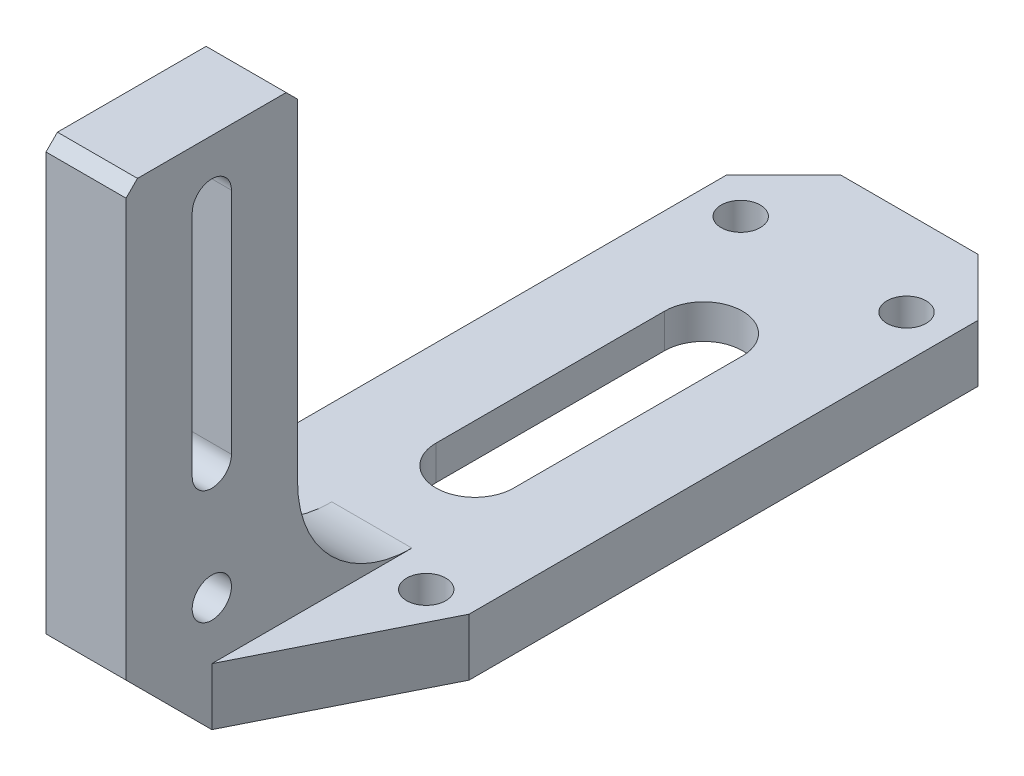
SolidWorks part; units mm, degrees
ref_plane "Front Plane" through (0, 0, 0) normal (0, 0, 1) x (1, 0, 0)
ref_plane "Top Plane" through (0, 0, 0) normal (0, 1, 0) x (1, 0, 0)
ref_plane "Right Plane" through (0, 0, 0) normal (1, 0, 0) x (0, 0, -1)
sketch "Sketch1" plane through (0, 0, 0) normal (0, 1, 0) x (1, 0, 0)
  line L1 (-11, -36) -> (11, -36)
  line L2 (-11, -36) -> (-11, 36)
  line L3 (-11, 36) -> (11, 36)
  line L4 (11, -36) -> (11, 36)
  line L5 (-11, -36) -> (11, 36) construction
  line L6 (-11, 36) -> (11, -36) construction
  point P0 (0, 0)
  dimension "D1" = 22
  dimension "D2" = 72
extrude "Boss-Extrude1" add sketch "Sketch1" along normal blind 5
sketch "Sketch2" plane through (0, 5, 0) normal (0, 1, 0) x (1, 0, 0)
  line L0 (-11, -36) -> (11, -36) construction
  line L1 (-3.5, -36) -> (3.5, -36)
  line L2 (-3.5, -36) -> (-3.5, -21)
  line L3 (-3.5, -21) -> (3.5, -21)
  line L4 (3.5, -36) -> (3.5, -21)
  line L5 (-11, 36) -> (-11, -36) construction
  dimension "D1" = 7
  dimension "D2" = 7.5
  dimension "D3" = 15
extrude "Boss-Extrude2" add sketch "Sketch2" along normal blind 40
chamfer "Chamfer1" distance 1 angle 45 2 edges at (0, 45, 36) (0, 45, 21)
fillet "Fillet1" radius 10 1 edges at (0, 5, 21)
sketch "Sketch5" plane through (0, 0, 0) normal (0, -1, 0) x (1, 0, 0)
  line L0 (11, -36) -> (-11, -36) construction
  line L2 (0, 2) -> (0, -18) construction
  line L3 (3.4, 2) -> (3.4, -18)
  line L4 (-3.4, 2) -> (-3.4, -18)
  line L5 (11, -36) -> (-11, -36) construction
  arc A1 (3.4, 2) -> (-3.4, 2) centre (0, 2) ccw
  arc A2 (-3.4, -18) -> (3.4, -18) centre (0, -18) ccw
  point P2 (0, -36)
  point P4 (0, -18)
  point P9 (0, -8)
  dimension "D2" = 3.4
  dimension "D1" = 18
  dimension "D3" = 20
extrude "Cut-Extrude2" cut sketch "Sketch5" against normal through all
sketch "Sketch6" plane through (0, 5, 0) normal (0, 1, 0) x (1, 0, 0)
  line L0 (11, -36) -> (11, 36) construction
  line L1 (3.5, -36) -> (11, -36)
  line L2 (3.5, -36) -> (3.5, -28.5)
  line L3 (3.5, -28.5) -> (11, -28.5)
  line L4 (11, -36) -> (11, -28.5)
  dimension "D1" = 7.5
extrude "Cut-Extrude3" cut sketch "Sketch6" against normal through all
mirror "Mirror1" about plane through (0, 0, 0) normal (1, 0, 0) of "Cut-Extrude3"
chamfer "Chamfer2" distance 15 distance2 7.5 1 edges at (11, 2.5, 28.5) first distance on face at (11, 2.5, -3.75)
chamfer "Chamfer7" distance 7.5 angle 45 1 edges at (0, 0, 36)
chamfer "Chamfer3" distance 5 angle 45 2 edges at (11, 2.5, -36) (-11, 2.5, -36)
sketch "Sketch8" plane through (0, 0, 0) normal (0, -1, 0) x (1, 0, 0)
  line L0 (0, 2) -> (0, -18) construction
  line L1 (8.5, 2) -> (8.5, -18)
  line L2 (-8.5, 2) -> (-8.5, -18)
  line L3 (-8.441, -19) -> (-6, -19)
  line L4 (-6, -19) -> (-6, 3)
  line L5 (-6, 3) -> (-8.441, 3)
  line L6 (0, -8) -> (-16.2177, -8) construction
  arc A0 (8.5, 2) -> (-8.5, 2) centre (0, 2) ccw
  arc A1 (-8.5, -18) -> (8.5, -18) centre (0, -18) ccw
  arc A2 (-3.4, -18) -> (3.4, -18) centre (0, -18) ccw construction
  arc A3 (3.4, 2) -> (-3.4, 2) centre (0, 2) ccw construction
  point P2 (0, -8)
  arc M6 (-3.4, 2) -> (3.4, 2) centre (0, 2) cw
  line M7 (3.4, 2) -> (3.4, -18)
  arc M8 (3.4, -18) -> (-3.4, -18) centre (0, -18) cw
  line M9 (-3.4, -18) -> (-3.4, 2)
  dimension "D1" = 8.5
  dimension "D2" = 22
  dimension "D3" = 6
extrude "Cut-Extrude6" cut sketch "Sketch8" against normal blind 2 contours L3 A1 L1 A0 L5 L4 M9 M6 M7 M8 | L2 A1 L3 L4 L5 A0 region at (8.0931, 0, -8) region at (-7.2491, 0, -8)
extrude "Cut-Extrude7" cut sketch "Sketch8<3>" against normal blind 4 contours L2 A1 L3 L4 L5 A0 region at (-7.2491, 0, -8)
sketch "Sketch8<3>" plane through (0, 0, 0) normal (0, -1, 0) x (1, 0, 0) same geometry as "Sketch8"
chamfer "Chamfer4" distance 2 angle 20 4 edges at (0, 0, 10.5) (-8.5, 0, -8) (8.5, 0, -8) (0, 0, -26.5) first distance on face at (-2.7376, 2, 5.081) first distance on face at (-8.5, 2, -8) first distance on face at (8.5, 1, -8) first distance on face at (-2.7376, 2, -21.081)
sketch "Sketch9" plane through (-3.5, 0, 0) normal (-1, 0, 0) x (0, 0, 1)
  line L0 (28.5, 20) -> (28.5, 40) construction
  line L1 (26.7855, 20) -> (26.7855, 40)
  line L2 (30.2145, 20) -> (30.2145, 40)
  line L4 (22, 45) -> (35, 45) construction
  line L5 (28.5, 45) -> (28.5, 50.0332) construction
  arc A0 (26.7855, 20) -> (30.2145, 20) centre (28.5, 20) ccw
  arc A1 (30.2145, 40) -> (26.7855, 40) centre (28.5, 40) ccw
  point P2 (28.5, 30)
  dimension "D2" = 1.7145
  dimension "D1" = 20
  dimension "D3" = 5
extrude "Cut-Extrude8" cut sketch "Sketch9" against normal through all
chamfer "Chamfer8" distance 7.5 distance2 15 1 edges at (-11, 2.5, 28.5) first distance on face at (-7.25, 2.5, 28.5)
sketch "Sketch12" plane through (3.5, 0, 0) normal (1, 0, 0) x (0, 0, -1)
  line L0 (-28.5, 18.2855) -> (-28.5, 14.746) construction
  circle A0 centre (-28.5, 10) radius 1.7145
  arc A1 (-30.2145, 20) -> (-26.7855, 20) centre (-28.5, 20) ccw construction
  dimension "D2" = 3.429
  dimension "D1" = 10
extrude "Cut-Extrude9" cut sketch "Sketch12" against normal through all
sketch "Sketch13" plane through (0, 5, 0) normal (0, 1, 0) x (1, 0, 0)
  line L0 (0, 0) -> (0, 7.4856) construction
  circle A0 centre (-7.25, -13.5) radius 1.7145
  circle A1 centre (7.25, -13.5) radius 1.7145
  circle A2 centre (-7.25, 28.5) radius 1.7145
  circle A3 centre (7.25, 28.5) radius 1.7145
  dimension "D1" = 3.429
  dimension "D2" = 7.25
  dimension "D3" = 42
extrude "Cut-Extrude10" cut sketch "Sketch13" against normal through all
